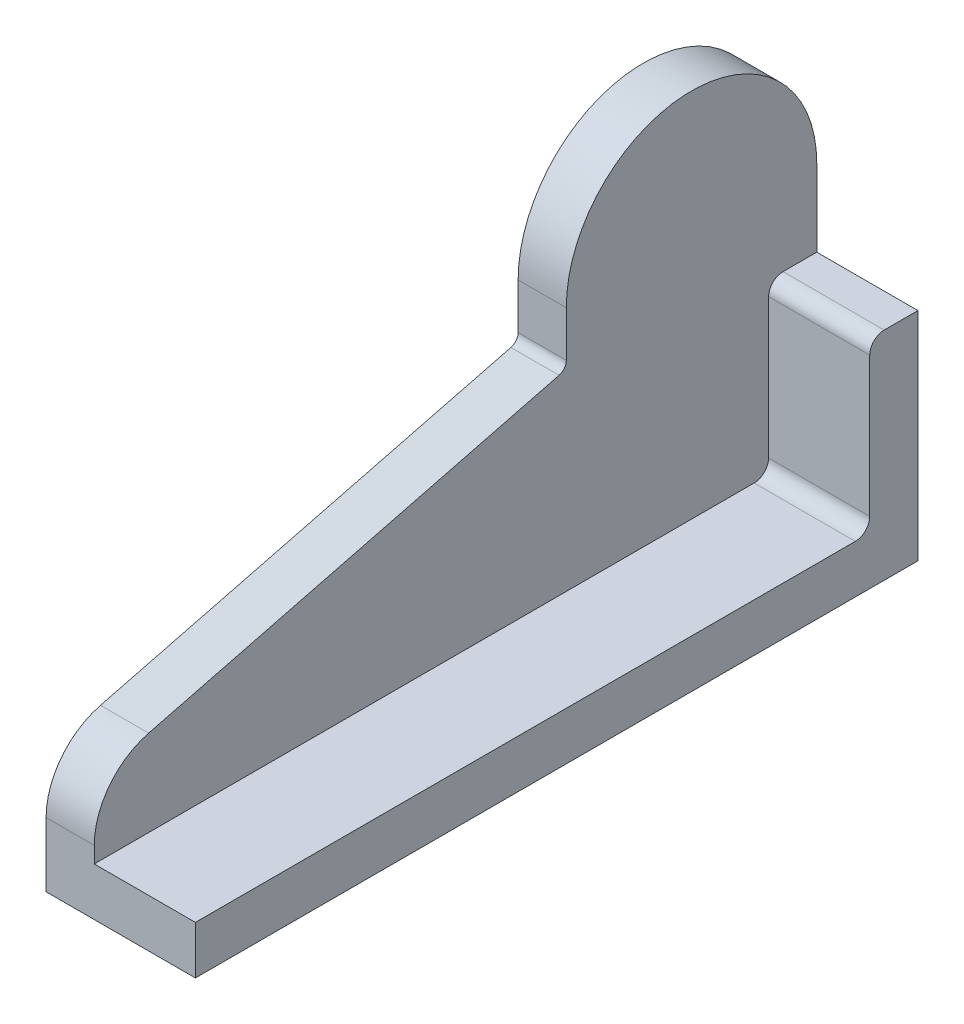
SolidWorks part; units mm, degrees
ref_plane "Front Plane" through (0, 0, 0) normal (0, 0, 1) x (1, 0, 0)
ref_plane "Top Plane" through (0, 0, 0) normal (0, 1, 0) x (1, 0, 0)
ref_plane "Right Plane" through (0, 0, 0) normal (1, 0, 0) x (0, 0, -1)
sketch "Sketch1" plane through (0, 0, 0) normal (0, 1, 0) x (1, 0, 0)
  line L1 (-41, -75) -> (41, -75)
  line L2 (-41, -75) -> (-41, 75)
  line L3 (-41, 75) -> (41, 75)
  line L4 (41, -75) -> (41, 75)
  line L5 (-41, -75) -> (41, 75) construction
  line L6 (-41, 75) -> (41, -75) construction
  point P0 (0, 0)
  dimension "D1" = 82
  dimension "D2" = 150
extrude "Boss-Extrude1" add sketch "Sketch1" along normal blind 10
sketch "Sketch2" plane through (41, 0, 0) normal (1, 0, 0) x (0, 0, -1)
  line L1 (75, 0) -> (65, 0)
  line L2 (75, 0) -> (75, 45)
  line L3 (75, 45) -> (65, 45)
  line L4 (65, 0) -> (65, 45)
  dimension "D1" = 10
  dimension "D2" = 45
extrude "Boss-Extrude2" add sketch "Sketch2" against normal through all
sketch "Sketch3" plane through (0, 0, -65) normal (0, 0, 1) x (1, 0, 0)
  line L0 (-41, 45) -> (41, 45) construction
  line L2 (10, 45) -> (10, 10)
  line L3 (10, 10) -> (20, 10)
  line L4 (20, 45) -> (20, 10)
  line L5 (-41, 10) -> (41, 10) construction
  line L6 (41, 45) -> (41, 10) construction
  line L7 (0, -55) -> (0, 55) construction
  line L9 (10, 45) -> (10, 87)
  line L10 (10, 87) -> (20, 87)
  line L11 (20, 45) -> (20, 87)
  line L12 (-10, 45) -> (-10, 87)
  line L13 (-10, 87) -> (-20, 87)
  line L14 (-20, 45) -> (-20, 87)
  line L15 (-20, 45) -> (-20, 10)
  line L16 (-10, 10) -> (-20, 10)
  line L17 (-10, 45) -> (-10, 10)
  dimension "D1" = 21
  dimension "D2" = 10
  dimension "D3" = 42
extrude "Boss-Extrude3" add sketch "Sketch3" along normal blind 42 and the other way blind 10
fillet "Fillet3" 2 edges at (15, 87, -23) (15, 87, -75) type full round first side face at (15, 48.5, -23) second side face at (0, 51.5, -75) middle face at (15, 87, -49)
fillet "Fillet4" 2 edges at (-15, 87, -23) (-15, 87, -75) type full round first side face at (-15, 48.5, -23) second side face at (0, 47.1667, -75) middle face at (-15, 87, -49)
sketch "Sketch4" plane through (20, 0, 0) normal (1, 0, 0) x (0, 0, -1)
  line L0 (23, 10) -> (23, 50)
  line L1 (23, 10) -> (23, 61) construction
  line L2 (23, 50) -> (-75, 25)
  line L3 (-75, 25) -> (-75, 10)
  line L4 (-75, 10) -> (23, 10)
  dimension "D1" = 15
  dimension "D2" = 40
extrude "Boss-Extrude4" add sketch "Sketch4" against normal up to surface (10 mm away) up to face at (10, 43, -54.3333)
sketch "Sketch5" plane through (-20, 0, 0) normal (-1, 0, 0) x (0, 0, 1)
  line L0 (-23, 50) -> (75, 25)
  line L1 (75, 25) -> (75, 10)
  line L2 (75, 10) -> (-23, 10)
  line L3 (-23, 10) -> (-23, 50)
extrude "Boss-Extrude5" add sketch "Sketch5" against normal up to surface (10 mm away) up to face at (-10, 43, -54.3333)
fillet "Fillet5" radius 15 1 edges at (15, 25, 75)
fillet "Fillet6" radius 15 1 edges at (-15, 25, 75)
sketch "Sketch6" plane through (20, 0, 0) normal (1, 0, 0) x (0, 0, -1)
  line L0 (65, 10) -> (-75, 10) construction
  line L1 (-75, 10) -> (-75, 0) construction
  circle A0 centre (49, 61) radius 8
  circle A1 centre (-60, 17.5) radius 5.5
  dimension "D1" = 7.5
  dimension "D3" = 11
  dimension "D2" = 15
extrude "Cut-Extrude1" cut sketch "Sketch6" against normal through all
fillet "Fillet7" radius 3 1 edges at (30.5, 45, -65)
fillet "Fillet8" radius 3 1 edges at (0, 45, -65)
fillet "Fillet9" radius 3 1 edges at (-30.5, 45, -65)
fillet "Fillet10" radius 3 3 edges at (-30.5, 10, -65) (0, 10, -65) (30.5, 10, -65)
fillet "Fillet11" radius 2 2 edges at (-15, 50, -23) (15, 50, -23)
sketch "Sketch7" plane through (0, 10, 0) normal (0, 1, 0) x (1, 0, 0)
  line L0 (20, 75) -> (41, 75) construction
  line L1 (20, 62) -> (20, -75) construction
  line L3 (20, 21.4944) -> (20, -63.7078) construction
  line L4 (0, -55) -> (0, 55) construction
  circle A0 centre (31.5, 45) radius 5.5
  circle A1 centre (31.5, -15) radius 5.5
  circle A2 centre (-31.5, -15) radius 5.5
  circle A3 centre (-31.5, 45) radius 5.5
  dimension "D1" = 30
  dimension "D3" = 11
  dimension "D4" = 11.5
  dimension "D6" = 11
  dimension "D2" = 11.5
  dimension "D5" = 60
extrude "Cut-Extrude2" cut sketch "Sketch7" against normal through all
ref_plane "Plane1" through (10, 0, 0) normal (-1, 0, 0) x (0, 0, 1)
sketch "Sketch8" plane through (10, 0, 0) normal (-1, 0, 0) x (0, 0, 1)
  line L1 (-89.0441, 92.3688) -> (92.0247, 92.3688)
  line L2 (-89.0441, 92.3688) -> (-89.0441, -6.921)
  line L3 (-89.0441, -6.921) -> (92.0247, -6.921)
  line L4 (92.0247, 92.3688) -> (92.0247, -6.921)
extrude "Cut-Extrude3" cut sketch "Sketch8" along normal through all
sketch "Sketch9" plane through (0, 10, 0) normal (0, 1, 0) x (1, 0, 0)
  line L1 (21.6428, 57.3757) -> (38.7591, 57.3757)
  line L2 (21.6428, 57.3757) -> (21.6428, -34.9558)
  line L3 (21.6428, -34.9558) -> (38.7591, -34.9558)
  line L4 (38.7591, 57.3757) -> (38.7591, -34.9558)
extrude "Boss-Extrude6" add sketch "Sketch9" against normal through all
sketch "Sketch10" plane through (10, 0, 0) normal (-1, 0, 0) x (0, 0, 1)
  line L1 (-60.17, 74.237) -> (-36.5118, 74.237)
  line L2 (-60.17, 74.237) -> (-60.17, 49.0885)
  line L3 (-60.17, 49.0885) -> (-36.5118, 49.0885)
  line L4 (-36.5118, 74.237) -> (-36.5118, 49.0885)
  line L5 (52.346, 24.1264) -> (66.3174, 24.1264)
  line L6 (52.346, 24.1264) -> (52.346, 9.4099)
  line L7 (52.346, 9.4099) -> (66.3174, 9.4099)
  line L8 (66.3174, 24.1264) -> (66.3174, 9.4099)
extrude "Boss-Extrude7" add sketch "Sketch10" against normal up to surface (10 mm away) up to face at (20, 61, -57)
